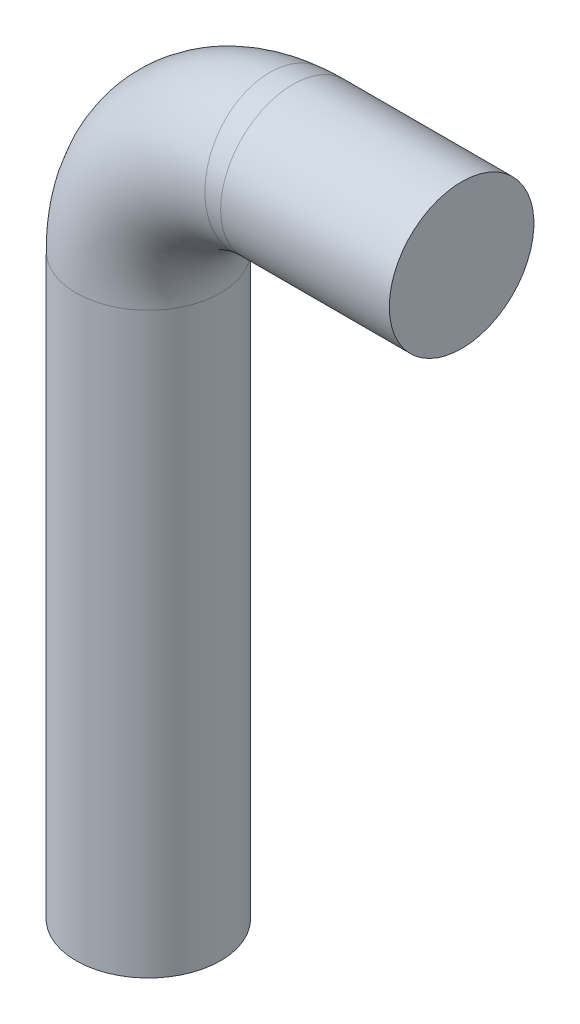
SolidWorks part; units mm, degrees
material "Plain Carbon Steel"
ref_plane "Front Plane" through (0, 0, 0) normal (0, 0, 1) x (1, 0, 0)
ref_plane "Top Plane" through (0, 0, 0) normal (0, 1, 0) x (1, 0, 0)
ref_plane "Right Plane" through (0, 0, 0) normal (1, 0, 0) x (0, 0, -1)
sketch "Sketch1" plane through (0, 0, 0) normal (0, 0, 1) x (1, 0, 0)
  spline S0 degree 1 poles (0, 0) (0, 12) knots 0 0 1 1 construction
  spline S1 degree 1 poles (0, 0) (0, 12) knots 0 0 1 1
  spline S2 degree 4 poles (0.0362, 11.5343) (0.0339, 11.5503) (0.0296, 11.581) (0.0216, 11.6309) (0.012, 11.7344) (0.0041, 11.809) (-0.0003, 11.9655) (-0.0004, 12.0319) (0.0038, 12.1817) (0.0122, 12.2722) (0.0248, 12.3964) (0.0415, 12.4998) (0.0624, 12.6146) (0.0874, 12.7213) (0.1164, 12.8313) (0.1495, 12.9377) (0.1958, 13.0706) (0.2593, 13.2263) (0.3445, 13.4035) (0.4569, 13.5979) (0.5834, 13.7836) (0.7235, 13.9591) (0.8761, 14.1238) (1.041, 14.2766) (1.2162, 14.4166) (1.4024, 14.5431) (1.5959, 14.6554) (1.7999, 14.7529) (2.0063, 14.835) (2.2255, 14.9012) (2.4366, 14.9511) (2.6441, 14.9804) (2.7909, 14.9951) (2.9663, 15.0004) (3.0358, 15.0003) (3.1896, 14.9959) (3.2666, 14.988) (3.3685, 14.9784) (3.4192, 14.9704) (3.4498, 14.9661) (3.4656, 14.9638) knots 0 0 0 0 0 0.010393 0.020785 0.041571 0.062104 0.082638 0.102512 0.122387 0.142261 0.162135 0.18201 0.201884 0.221758 0.241633 0.261507 0.281382 0.32113 0.360879 0.400628 0.440377 0.480126 0.519874 0.559623 0.599372 0.639121 0.67887 0.718618 0.758367 0.798116 0.837865 0.877613 0.897488 0.917362 0.937896 0.958429 0.979215 0.989607 1 1 1 1 1 construction
  spline S3 degree 4 poles (0, 12) (0, 12.0234) (0.0007, 12.0703) (0.0038, 12.1817) (0.0122, 12.2722) (0.0248, 12.3964) (0.0415, 12.4998) (0.0624, 12.6146) (0.0874, 12.7213) (0.1164, 12.8313) (0.1495, 12.9377) (0.1958, 13.0706) (0.2593, 13.2263) (0.3445, 13.4035) (0.4569, 13.5979) (0.5834, 13.7836) (0.7235, 13.9591) (0.8761, 14.1238) (1.041, 14.2766) (1.2162, 14.4166) (1.4024, 14.5431) (1.5959, 14.6554) (1.7999, 14.7529) (2.0063, 14.835) (2.2255, 14.9012) (2.4366, 14.9511) (2.6441, 14.9804) (2.7909, 14.9951) (2.9303, 14.9993) (2.9766, 15) (3, 15) knots 0.082638 0.082638 0.082638 0.082638 0.082638 0.102512 0.122387 0.142261 0.162135 0.18201 0.201884 0.221758 0.241633 0.261507 0.281382 0.32113 0.360879 0.400628 0.440377 0.480126 0.519874 0.559623 0.599372 0.639121 0.67887 0.718618 0.758367 0.798116 0.837865 0.877613 0.897488 0.917362 0.917362 0.917362 0.917362 0.917362
  spline S4 degree 1 poles (3, 15) (6.5, 15) knots 0 0 1 1 construction
  spline S5 degree 1 poles (3, 15) (6.5, 15) knots 0 0 1 1
sketch "Sketch2" plane through (0, 0, 0) normal (0, 1, 0) x (1, 0, 0)
  circle A0 centre (0, 0) radius 1.5
  dimension "D1" = 3
sweep "Sweep1" add profiles "Sketch2" path "Sketch1"
